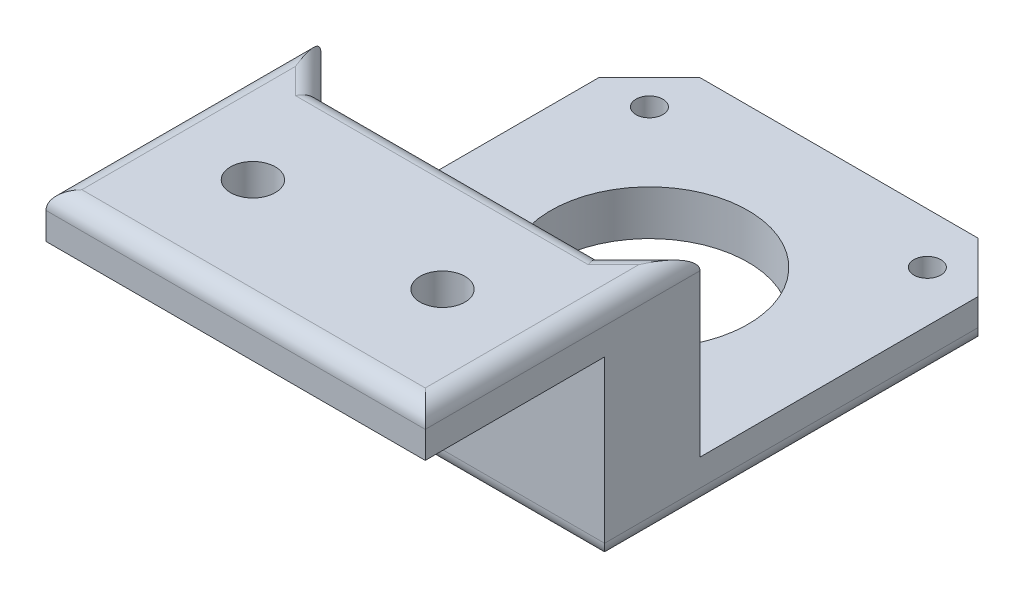
SolidWorks part; units mm, degrees
ref_plane "정면" through (0, 0, 0) normal (0, 0, 1) x (1, 0, 0)
ref_plane "윗면" through (0, 0, 0) normal (0, 1, 0) x (1, 0, 0)
ref_plane "우측면" through (0, 0, 0) normal (1, 0, 0) x (0, 0, -1)
sketch "스케치1" plane through (0, 0, 0) normal (1, 0, 0) x (0, 0, -1)
  line L1 (0, 0) -> (20, 0)
  line L2 (0, 0) -> (0, 5)
  line L3 (0, 5) -> (20, 5)
  line L4 (20, 0) -> (20, 5)
  line L5 (20, 5) -> (25, 5)
  line L6 (20, 5) -> (20, -20)
  line L7 (20, -20) -> (25, -20)
  line L8 (25, 5) -> (25, -20)
  line L9 (25, -20) -> (67.3, -20)
  line L10 (25, -20) -> (25, -15)
  line L11 (25, -15) -> (67.3, -15)
  line L12 (67.3, -20) -> (67.3, -15)
  dimension "D1" = 5
  dimension "D2" = 20
  dimension "D3" = 20
  dimension "D4" = 5
  dimension "D5" = 42.3
extrude "보스-돌출1" add sketch "스케치1" along normal blind 42.3 contours L9 L12 L11 L8 | L8 L5 L4 L6 L7 | L4 L1 L2 L3 region at (0, -7.5, -22.5) region at (0, -17.5, -46.15)
sketch "스케치2" plane through (0, 5, 0) normal (0, 1, 0) x (1, 0, 0)
  line L0 (0, 12.5) -> (42.3, 12.5) construction
  line L1 (0, 0) -> (0, 25) construction
  line L2 (42.3, 0) -> (42.3, 25) construction
  line L3 (21.15, 25) -> (21.15, 0) construction
  line L4 (42.3, 25) -> (0, 25) construction
  line L5 (42.3, 0) -> (0, 0) construction
  line L6 (10.575, 25) -> (10.575, 0) construction
  line L7 (31.725, 25) -> (31.725, 0) construction
  line L8 (0, 46.15) -> (42.3, 46.15) construction
  line L9 (21.15, 67.3) -> (21.15, 25) construction
  line L10 (42.3, 67.3) -> (0, 67.3) construction
  line L11 (0, 25) -> (0, 67.3) construction
  line L12 (42.3, 25) -> (42.3, 67.3) construction
  line L13 (5.65, 67.3) -> (0, 61.65)
  line L14 (5.65, 30.65) -> (36.65, 30.65)
  line L15 (5.65, 30.65) -> (5.65, 61.65)
  line L16 (5.65, 61.65) -> (36.65, 61.65)
  line L17 (36.65, 30.65) -> (36.65, 61.65)
  line L18 (5.65, 30.65) -> (36.65, 61.65) construction
  line L19 (5.65, 61.65) -> (36.65, 30.65) construction
  line L20 (36.65, 67.3) -> (42.3, 61.65)
  line L21 (36.65, 25) -> (42.3, 30.65)
  line L22 (5.65, 25) -> (0, 30.65)
  line L23 (0, 67.3) -> (0, 25)
  line L24 (0, 25) -> (42.3, 25)
  line L25 (42.3, 25) -> (42.3, 67.3)
  line L26 (42.3, 67.3) -> (0, 67.3)
  line L27 (0, 61.65) -> (0, 35)
  line L28 (10, 25) -> (32.3, 25)
  line L29 (42.3, 35) -> (42.3, 57.3)
  line L30 (32.3, 67.3) -> (5.65, 67.3)
  line L44 (0, 25) -> (42.3, 25)
  line L45 (0, 25) -> (0, 67.3)
  line L46 (0, 67.3) -> (42.3, 67.3)
  line L47 (42.3, 25) -> (42.3, 67.3)
  circle A0 centre (10.575, 12.5) radius 2.5
  circle A1 centre (31.725, 12.5) radius 2.5
  circle A2 centre (5.65, 61.65) radius 1.5
  circle A3 centre (5.65, 30.65) radius 1.5
  circle A4 centre (36.65, 30.65) radius 1.5
  circle A5 centre (36.65, 61.65) radius 1.5
  circle A6 centre (21.15, 46.15) radius 11
  point P29 (21.15, 46.15)
  line M4 (42.3, 25) -> (0, 25)
  dimension "D2" = 5
  dimension "D4" = 3
  dimension "D6" = 22
  dimension "D1" = 10.575
  dimension "D3" = 31
  dimension "D5" = 0
extrude "컷-돌출1" cut sketch "스케치2" against normal through all contours L46 L45 L13 | L20 L47 L46 | A6 | A2 | A5 | A3 | A4 | A0 | A1 region at (1.8833, 5, -65.4167) region at (40.4167, 5, -65.4167) region at (21.15, 5, -46.15)
extrude "보스-돌출2" add sketch "스케치2<4>" against normal up to vertex (20 mm away) contours L45 L22 M4 | L47 L21 M4 region at (1.8833, 5, -26.8833) region at (40.4167, 5, -26.8833) up to point (0, -15, -25)
sketch "스케치2<4>" plane through (0, 5, 0) normal (0, 1, 0) x (1, 0, 0) same geometry as "스케치2"
fillet "필렛1" radius 2 10 edges at (21.15, -20, -67.3) (42.3, -20, -40.825) (0, -20, -40.825) (21.15, -20, -20) (2.825, 5, -27.825) (21.15, 5, -25) (39.475, 5, -27.825) (21.15, 5, 0) (0, 5, -15.325) (42.3, 5, -15.325)
